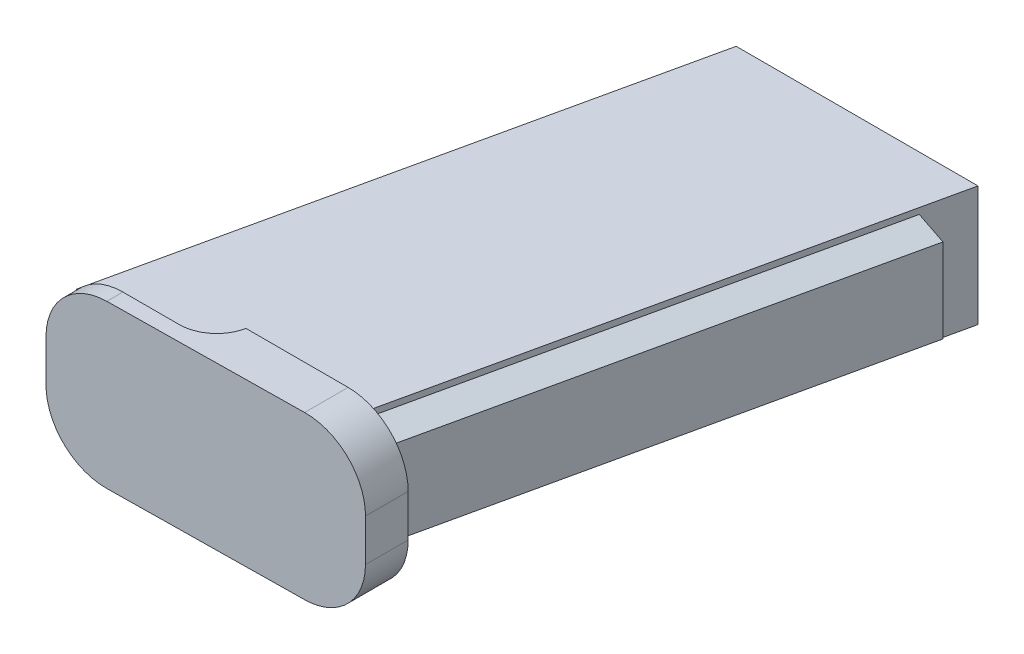
SolidWorks part; units mm, degrees
ref_plane "前视基准面" through (0, 0, 0) normal (0, 0, 1) x (1, 0, 0)
ref_plane "上视基准面" through (0, 0, 0) normal (0, 1, 0) x (1, 0, 0)
ref_plane "右视基准面" through (0, 0, 0) normal (1, 0, 0) x (0, 0, -1)
sketch "草图2" plane through (0, 0, 0) normal (0, 1, 0) x (1, 0, 0)
  line L0 (58.1866, 206.9702) -> (416.9669, 206.9702) construction
  line L1 (208, 447.7092) -> (208, -77.9206) construction
  dimension "D1" = 208
sketch "草图3" plane through (0, 0, 0) normal (0, 1, 0) x (1, 0, 0)
  line L0 (213.3409, 89.8604) -> (216.8796, 89.8604)
  line L1 (216.8796, 89.8604) -> (218.2246, 95.937)
  line L2 (218.2246, 95.937) -> (254.949, 95.937)
  line L3 (254.949, 95.937) -> (273.7623, 180.937)
  line L4 (273.7623, 180.937) -> (233.4992, 180.937)
  line L5 (233.4992, 180.937) -> (213.3409, 89.8604)
  dimension "D1" = 85
  dimension "D2" = 102.48
extrude "凸台-拉伸1" add sketch "草图3" along normal blind 10 and the other way blind 10
sketch "草图5" plane through (0, 0, 0) normal (0, 1, 0) x (1, 0, 0)
  line L0 (271.9917, 172.937) -> (275.9182, 172.937)
  line L1 (254.949, 95.937) -> (273.7623, 180.937) construction
  line L2 (275.9182, 172.937) -> (258.8755, 95.937)
  line L3 (258.8755, 95.937) -> (254.949, 95.937)
  line L4 (271.9917, 172.937) -> (254.949, 95.937)
  dimension "D1" = 8
extrude "凸台-拉伸2" add sketch "草图5" along normal up to vertex (10 mm away) and the other way up to vertex (10 mm away) up to point (273.7623, 10, -180.937) other way up to point (273.7623, -10, -180.937)
sketch "草图6" plane through (0, 0, -172.937) normal (0, 0, -1) x (-1, 0, 0)
  line L2 (-275.9182, 10) -> (-275.9182, -10) construction
  line L4 (-271.9917, 0) -> (-275.9182, 0) construction
  line L5 (-271.9917, 10) -> (-271.9917, -10) construction
  line L9 (-275.9182, 7) -> (-271.9917, 9)
  line L10 (-271.9917, 9) -> (-271.9917, 10)
  line L11 (-271.9917, 10) -> (-275.9182, 10)
  line L12 (-275.9182, 10) -> (-275.9182, 7)
  line L13 (-271.9917, -9) -> (-271.9917, -10)
  line L14 (-271.9917, -10) -> (-275.9182, -10)
  line L15 (-275.9182, -10) -> (-275.9182, -7)
  line L16 (-275.9182, -7) -> (-271.9917, -9)
  dimension "D1" = 1
  dimension "D2" = 3
extrude "切除-拉伸1" cut sketch "草图6" along direction (0.2161, 0, -0.9764) on the side against the normal up to vertex (77 mm away) up to point (258.8755, 10, -95.937)
sketch "草图7" plane through (0, 0, 0) normal (0, 1, 0) x (1, 0, 0)
  line L0 (229.0489, 90.967) -> (197.9297, 90.967)
  line L4 (197.9297, 90.967) -> (197.9297, 83.277)
  line L5 (197.9297, 83.277) -> (229.0489, 83.277)
  line L6 (229.0489, 83.277) -> (229.0489, 90.967)
  line L7 (218.2246, 95.937) -> (254.949, 95.937) construction
  dimension "D1" = 4.97
extrude "切除-拉伸2" cut sketch "草图7" against normal through all and the other way through all
sketch "草图8" plane through (0, 0, -95.937) normal (0, 0, 1) x (1, 0, 0)
  line L0 (258.8755, 0) -> (-49741.1245, 0) construction
  line L1 (236.3755, 0) -> (236.3755, -50000) construction
  line L2 (253.8755, 13.5) -> (221.3755, 13.5)
  line L3 (258.8755, 7) -> (258.8755, -7) construction
  line L4 (253.8755, -13.5) -> (221.3755, -13.5)
  line L5 (263.8755, 3.5) -> (263.8755, -3.5)
  line L6 (211.3755, 3.5) -> (211.3755, -3.5)
  arc A0 (253.8755, -13.5) -> (263.8755, -3.5) centre (253.8755, -3.5) ccw
  arc A1 (221.3755, -13.5) -> (211.3755, -3.5) centre (221.3755, -3.5) cw
  arc A2 (221.3755, 13.5) -> (211.3755, 3.5) centre (221.3755, 3.5) ccw
  arc A3 (253.8755, 13.5) -> (263.8755, 3.5) centre (253.8755, 3.5) cw
  point P4 (258.8755, 0)
  point P15 (208.7217, 0)
  point P16 (208.9752, 0)
  point P18 (211.3755, 0)
  point P23 (263.8755, 0)
  dimension "D1" = 10
  dimension "D2" = 10
  dimension "D3" = 52.5
  dimension "D4" = 13.5
  dimension "D5" = 22.5
  dimension "D6" = 27.5
extrude "凸台-拉伸3" add sketch "草图8" along normal blind 15
sketch "草图11" plane through (0, 0, 0) normal (0, 1, 0) x (1, 0, 0)
  line L0 (270.8704, 64.9713) -> (324.1781, 65.6807) construction
  line L1 (268.0627, 88.8847) -> (201.6581, 88.0009)
  line L2 (201.6581, 88.0009) -> (201.6581, 68.7706)
  line L3 (201.6581, 68.7706) -> (268.0627, 68.7706)
  line L4 (268.0627, 68.7706) -> (268.0627, 88.8847)
  point P2 (0, 0)
  point P7 (270.8834, 63.9935)
  point P8 (267.6433, 86.503)
  point P9 (0, 0)
  point P10 (268.0627, 88.8847)
extrude "切除-拉伸3" cut sketch "草图11" against normal through all and the other way through all
sketch "草图13" plane through (0, 13.5, 0) normal (0, 1, 0) x (1, 0, 0)
  line L0 (208, 90.937) -> (230.7574, 90.937)
  line L1 (253.8755, 95.937) -> (221.3755, 95.937) construction
  line L2 (236.8755, 95.937) -> (236.8755, 103.3047)
  line L3 (263.8755, 88.8289) -> (263.8755, 95.937) construction
  line L4 (208, 200447.7092) -> (208, -200077.9206) construction
  line L5 (236.8755, 103.3047) -> (208, 103.3047)
  line L6 (208, 103.3047) -> (208, 90.937)
  arc A0 (230.7574, 90.937) -> (236.8755, 95.937) centre (230.7574, 97.1801) ccw
  point P9 (0, 0)
  point P12 (231.1743, 96.6874)
  point P14 (231.5266, 96.2981)
  point P15 (230.7574, 97.1801)
  dimension "D1" = 27
  dimension "D2" = 5
extrude "切除-拉伸4" cut sketch "草图13" against normal up to vertex (3.5 mm away) up to point (214.6859, 10, -95.937)
mirror "镜向1" about plane through (0, 0, 0) normal (0, 1, 0) of "切除-拉伸4"
sketch "草图14" plane through (0, 0, -95.937) normal (0, 0, -1) x (-1, 0, 0)
  line L0 (-213.7762, -10) -> (-214.6859, -10)
  line L1 (-214.6859, -10) -> (-214.6859, 10)
  line L2 (-214.6859, 10) -> (-213.7762, 10)
  line L3 (-211.3755, 3.5) -> (-211.3755, -3.5) construction
  line L4 (-211.3755, -3.5) -> (-211.3755, 3.5)
  arc A0 (-213.7762, 10) -> (-211.3755, 3.5) centre (-221.3755, 3.5) cw
  arc A1 (-213.7762, -10) -> (-211.3755, -3.5) centre (-221.3755, -3.5) ccw
  arc A2 (-213.7762, -10) -> (-211.3755, -3.5) centre (-221.3755, -3.5) ccw construction
extrude "切除-拉伸5" cut sketch "草图14" along direction (-0.2161, 0, 0.9764) on the side against the normal up to vertex (5 mm away) up to point (213.7762, 10, -90.937)
